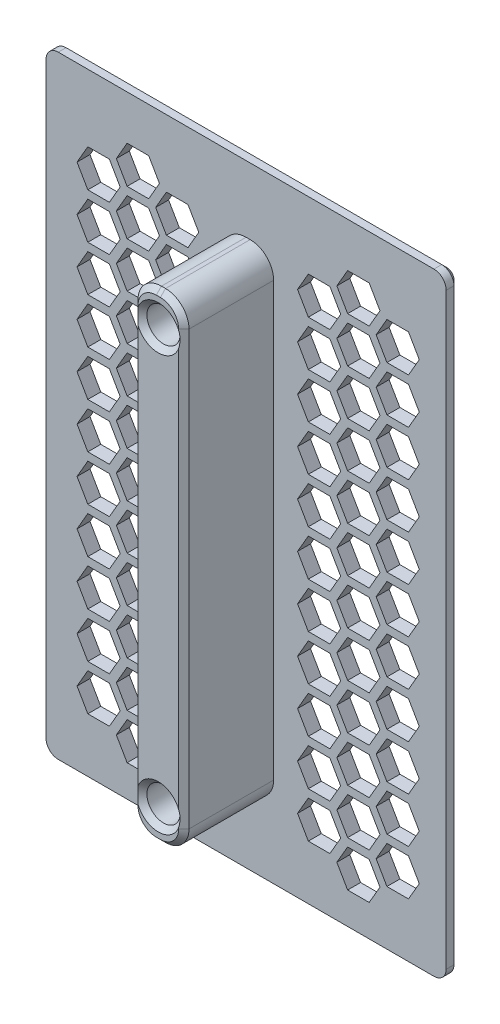
SolidWorks part; units mm, degrees
ref_plane "Front Plane" through (0, 0, 0) normal (0, 0, 1) x (1, 0, 0)
ref_plane "Top Plane" through (0, 0, 0) normal (0, 1, 0) x (1, 0, 0)
ref_plane "Right Plane" through (0, 0, 0) normal (1, 0, 0) x (0, 0, -1)
sketch "Sketch1" plane through (0, 0, 0) normal (0, 0, 1) x (1, 0, 0)
  line L0 (24.5, 37.5) -> (-24.5, 37.5) construction
  line L1 (24.5, -37.5) -> (-24.5, -37.5)
  line L2 (24.5, -37.5) -> (24.5, 37.5)
  line L3 (24.5, 37.5) -> (-24.5, 37.5)
  line L4 (-24.5, -37.5) -> (-24.5, 37.5)
  line L5 (24.5, -37.5) -> (-24.5, 37.5) construction
  line L6 (24.5, 37.5) -> (-24.5, -37.5) construction
  line L7 (24.5, 37.5) -> (24.5, -37.5) construction
  point P0 (0, 0)
extrude "Boss-Extrude1" add sketch "Sketch1" along normal blind 1.5875
sketch "Sketch2" plane through (0, 0, 1.5875) normal (0, 0, 1) x (1, 0, 0)
  line L12 (0.5, 29.5) -> (0, 29.5) construction
  line L13 (-3, 26.5) -> (-3, -26.5) construction
  line L14 (3.5, -26.5) -> (3.5, 26.5) construction
  line L15 (0, -29.5) -> (0.5, -29.5) construction
  line L16 (0.5, 29.5) -> (0, 29.5)
  line L17 (-3, 26.5) -> (-3, -26.5)
  line L18 (3.5, -26.5) -> (3.5, 26.5)
  line L19 (0, -29.5) -> (0.5, -29.5)
  line L20 (-2.873, 26.5) -> (-2.873, -26.5)
  line L21 (0, -29.373) -> (0.5, -29.373)
  line L22 (3.373, -26.5) -> (3.373, 26.5)
  line L23 (0.5, 29.373) -> (0, 29.373)
  arc A12 (3.5, 26.5) -> (0.5, 29.5) centre (0.5, 26.5) ccw construction
  arc A13 (0, 29.5) -> (-3, 26.5) centre (0, 26.5) ccw construction
  arc A14 (0.5, -29.5) -> (3.5, -26.5) centre (0.5, -26.5) ccw construction
  arc A15 (-3, -26.5) -> (0, -29.5) centre (0, -26.5) ccw construction
  arc A16 (3.5, 26.5) -> (0.5, 29.5) centre (0.5, 26.5) ccw
  arc A17 (0, 29.5) -> (-3, 26.5) centre (0, 26.5) ccw
  arc A18 (0.5, -29.5) -> (3.5, -26.5) centre (0.5, -26.5) ccw
  arc A19 (-3, -26.5) -> (0, -29.5) centre (0, -26.5) ccw
  arc A20 (0, 29.373) -> (-2.873, 26.5) centre (0, 26.5) ccw
  arc A21 (-2.873, -26.5) -> (0, -29.373) centre (0, -26.5) ccw
  arc A22 (0.5, -29.373) -> (3.373, -26.5) centre (0.5, -26.5) ccw
  arc A23 (3.373, 26.5) -> (0.5, 29.373) centre (0.5, 26.5) ccw
  dimension "D1" = 0.127
extrude "Boss-Extrude2" add sketch "Sketch2" along normal up to surface (11 mm away) contours L22 A23 L23 A20 L20 A21 L21 A22 region at (0.25, 0, 1.5875)
sketch "Sketch3" plane through (0, 0, 12.5875) normal (0, 0, 1) x (1, 0, 0)
  line L1 (0.25, 25.4) -> (0.25, -25.4) construction
  line L3 (-2.873, 0) -> (3.373, 0) construction
  line L4 (-2.873, -26.5) -> (-2.873, 26.5) construction
  line L5 (3.373, 26.5) -> (3.373, -26.5) construction
  circle A0 centre (0.25, 25.4) radius 2.032
  circle A1 centre (0.25, -25.4) radius 2.032
  point P13 (0.25, 0)
  point P14 (0, 0)
  dimension "D1" = 4.064
  dimension "D2" = 50.8
extrude "Cut-Extrude1" cut sketch "Sketch3" against normal blind 9.525
fillet "Fillet1" radius 1.5 4 edges at (24.5, -37.5, 0.7937) (-24.5, -37.5, 0.7937) (-24.5, 37.5, 0.7937) (24.5, 37.5, 0.7937)
sketch "Sketch4" plane through (0, 0, 0) normal (0, 0, -1) x (-1, 0, 0)
  line L0 (-18.5619, -28.5679) -> (-13.75, -31.346) construction
  line L1 (-16.3896, -31.346) -> (-15.0698, -33.632)
  line L2 (-15.0698, -33.632) -> (-12.4302, -33.632)
  line L3 (-12.4302, -33.632) -> (-11.1104, -31.346)
  line L4 (-11.1104, -31.346) -> (-12.4302, -29.06)
  line L5 (-12.4302, -29.06) -> (-15.0698, -29.06)
  line L6 (-15.0698, -29.06) -> (-16.3896, -31.346)
  line L7 (-21.2015, -28.5679) -> (-19.8817, -30.8539)
  line L8 (-19.8817, -30.8539) -> (-17.242, -30.8539)
  line L9 (-17.242, -30.8539) -> (-15.9222, -28.5679)
  line L10 (-15.9222, -28.5679) -> (-17.242, -26.2819)
  line L11 (-17.242, -26.2819) -> (-19.8817, -26.2819)
  line L12 (-19.8817, -26.2819) -> (-21.2015, -28.5679)
  line L13 (-10.258, -30.8539) -> (-7.6183, -30.8539)
  line L14 (-7.6183, -30.8539) -> (-6.2985, -28.5679)
  line L15 (-6.2985, -28.5679) -> (-7.6183, -26.2819)
  line L16 (-7.6183, -26.2819) -> (-10.258, -26.2819)
  line L17 (-10.258, -26.2819) -> (-11.5778, -28.5679)
  line L18 (-11.5778, -28.5679) -> (-10.258, -30.8539)
  line L19 (-11.1104, -31.346) -> (-10.258, -30.8539) construction
  line L20 (-13.75, -31.346) -> (-8.9381, -28.5679) construction
  line L21 (-4.5, -26.832) -> (-23, -26.832) construction
  line L22 (-10.258, -20.7257) -> (-11.5778, -23.0117)
  line L23 (-7.6183, -20.7257) -> (-10.258, -20.7257)
  line L24 (-6.2985, -23.0117) -> (-7.6183, -20.7257)
  line L25 (-7.6183, -25.2977) -> (-6.2985, -23.0117)
  line L26 (-10.258, -25.2977) -> (-7.6183, -25.2977)
  line L27 (-11.5778, -23.0117) -> (-10.258, -25.2977)
  line L28 (-11.1104, -25.7898) -> (-12.4302, -23.5038)
  line L29 (-12.4302, -23.5038) -> (-15.0698, -23.5038)
  line L30 (-15.0698, -23.5038) -> (-16.3896, -25.7898)
  line L31 (-16.3896, -25.7898) -> (-15.0698, -28.0758)
  line L32 (-15.0698, -28.0758) -> (-12.4302, -28.0758)
  line L33 (-12.4302, -28.0758) -> (-11.1104, -25.7898)
  line L34 (-17.242, -25.2977) -> (-15.9222, -23.0117)
  line L35 (-15.9222, -23.0117) -> (-17.242, -20.7257)
  line L36 (-17.242, -20.7257) -> (-19.8817, -20.7257)
  line L37 (-19.8817, -20.7257) -> (-21.2015, -23.0117)
  line L38 (-21.2015, -23.0117) -> (-19.8817, -25.2977)
  line L39 (-19.8817, -25.2977) -> (-17.242, -25.2977)
  line L40 (-10.258, -15.1694) -> (-11.5778, -17.4554)
  line L41 (-7.6183, -15.1694) -> (-10.258, -15.1694)
  line L42 (-6.2985, -17.4554) -> (-7.6183, -15.1694)
  line L43 (-7.6183, -19.7414) -> (-6.2985, -17.4554)
  line L44 (-10.258, -19.7414) -> (-7.6183, -19.7414)
  line L45 (-11.5778, -17.4554) -> (-10.258, -19.7414)
  line L46 (-11.1104, -20.2335) -> (-12.4302, -17.9475)
  line L47 (-12.4302, -17.9475) -> (-15.0698, -17.9475)
  line L48 (-15.0698, -17.9475) -> (-16.3896, -20.2335)
  line L49 (-16.3896, -20.2335) -> (-15.0698, -22.5195)
  line L50 (-15.0698, -22.5195) -> (-12.4302, -22.5195)
  line L51 (-12.4302, -22.5195) -> (-11.1104, -20.2335)
  line L52 (-17.242, -19.7414) -> (-15.9222, -17.4554)
  line L53 (-15.9222, -17.4554) -> (-17.242, -15.1694)
  line L54 (-17.242, -15.1694) -> (-19.8817, -15.1694)
  line L55 (-19.8817, -15.1694) -> (-21.2015, -17.4554)
  line L56 (-21.2015, -17.4554) -> (-19.8817, -19.7414)
  line L57 (-19.8817, -19.7414) -> (-17.242, -19.7414)
  line L58 (-10.258, -9.6132) -> (-11.5778, -11.8992)
  line L59 (-7.6183, -9.6132) -> (-10.258, -9.6132)
  line L60 (-6.2985, -11.8992) -> (-7.6183, -9.6132)
  line L61 (-7.6183, -14.1852) -> (-6.2985, -11.8992)
  line L62 (-10.258, -14.1852) -> (-7.6183, -14.1852)
  line L63 (-11.5778, -11.8992) -> (-10.258, -14.1852)
  line L64 (-11.1104, -14.6773) -> (-12.4302, -12.3913)
  line L65 (-12.4302, -12.3913) -> (-15.0698, -12.3913)
  line L66 (-15.0698, -12.3913) -> (-16.3896, -14.6773)
  line L67 (-16.3896, -14.6773) -> (-15.0698, -16.9633)
  line L68 (-15.0698, -16.9633) -> (-12.4302, -16.9633)
  line L69 (-12.4302, -16.9633) -> (-11.1104, -14.6773)
  line L70 (-17.242, -14.1852) -> (-15.9222, -11.8992)
  line L71 (-15.9222, -11.8992) -> (-17.242, -9.6132)
  line L72 (-17.242, -9.6132) -> (-19.8817, -9.6132)
  line L73 (-19.8817, -9.6132) -> (-21.2015, -11.8992)
  line L74 (-21.2015, -11.8992) -> (-19.8817, -14.1852)
  line L75 (-19.8817, -14.1852) -> (-17.242, -14.1852)
  line L76 (-10.258, -4.0569) -> (-11.5778, -6.3429)
  line L77 (-7.6183, -4.0569) -> (-10.258, -4.0569)
  line L78 (-6.2985, -6.3429) -> (-7.6183, -4.0569)
  line L79 (-7.6183, -8.6289) -> (-6.2985, -6.3429)
  line L80 (-10.258, -8.6289) -> (-7.6183, -8.6289)
  line L81 (-11.5778, -6.3429) -> (-10.258, -8.6289)
  line L82 (-11.1104, -9.121) -> (-12.4302, -6.835)
  line L83 (-12.4302, -6.835) -> (-15.0698, -6.835)
  line L84 (-15.0698, -6.835) -> (-16.3896, -9.121)
  line L85 (-16.3896, -9.121) -> (-15.0698, -11.407)
  line L86 (-15.0698, -11.407) -> (-12.4302, -11.407)
  line L87 (-12.4302, -11.407) -> (-11.1104, -9.121)
  line L88 (-17.242, -8.6289) -> (-15.9222, -6.3429)
  line L89 (-15.9222, -6.3429) -> (-17.242, -4.0569)
  line L90 (-17.242, -4.0569) -> (-19.8817, -4.0569)
  line L91 (-19.8817, -4.0569) -> (-21.2015, -6.3429)
  line L92 (-21.2015, -6.3429) -> (-19.8817, -8.6289)
  line L93 (-19.8817, -8.6289) -> (-17.242, -8.6289)
  line L94 (-10.258, 1.4993) -> (-11.5778, -0.7867)
  line L95 (-7.6183, 1.4993) -> (-10.258, 1.4993)
  line L96 (-6.2985, -0.7867) -> (-7.6183, 1.4993)
  line L97 (-7.6183, -3.0727) -> (-6.2985, -0.7867)
  line L98 (-10.258, -3.0727) -> (-7.6183, -3.0727)
  line L99 (-11.5778, -0.7867) -> (-10.258, -3.0727)
  line L100 (-11.1104, -3.5648) -> (-12.4302, -1.2788)
  line L101 (-12.4302, -1.2788) -> (-15.0698, -1.2788)
  line L102 (-15.0698, -1.2788) -> (-16.3896, -3.5648)
  line L103 (-16.3896, -3.5648) -> (-15.0698, -5.8508)
  line L104 (-15.0698, -5.8508) -> (-12.4302, -5.8508)
  line L105 (-12.4302, -5.8508) -> (-11.1104, -3.5648)
  line L106 (-17.242, -3.0727) -> (-15.9222, -0.7867)
  line L107 (-15.9222, -0.7867) -> (-17.242, 1.4993)
  line L108 (-17.242, 1.4993) -> (-19.8817, 1.4993)
  line L109 (-19.8817, 1.4993) -> (-21.2015, -0.7867)
  line L110 (-21.2015, -0.7867) -> (-19.8817, -3.0727)
  line L111 (-19.8817, -3.0727) -> (-17.242, -3.0727)
  line L112 (-10.258, 7.0556) -> (-11.5778, 4.7696)
  line L113 (-7.6183, 7.0556) -> (-10.258, 7.0556)
  line L114 (-6.2985, 4.7696) -> (-7.6183, 7.0556)
  line L115 (-7.6183, 2.4836) -> (-6.2985, 4.7696)
  line L116 (-10.258, 2.4836) -> (-7.6183, 2.4836)
  line L117 (-11.5778, 4.7696) -> (-10.258, 2.4836)
  line L118 (-11.1104, 1.9915) -> (-12.4302, 4.2775)
  line L119 (-12.4302, 4.2775) -> (-15.0698, 4.2775)
  line L120 (-15.0698, 4.2775) -> (-16.3896, 1.9915)
  line L121 (-16.3896, 1.9915) -> (-15.0698, -0.2945)
  line L122 (-15.0698, -0.2945) -> (-12.4302, -0.2945)
  line L123 (-12.4302, -0.2945) -> (-11.1104, 1.9915)
  line L124 (-17.242, 2.4836) -> (-15.9222, 4.7696)
  line L125 (-15.9222, 4.7696) -> (-17.242, 7.0556)
  line L126 (-17.242, 7.0556) -> (-19.8817, 7.0556)
  line L127 (-19.8817, 7.0556) -> (-21.2015, 4.7696)
  line L128 (-21.2015, 4.7696) -> (-19.8817, 2.4836)
  line L129 (-19.8817, 2.4836) -> (-17.242, 2.4836)
  line L130 (-10.258, 12.6118) -> (-11.5778, 10.3258)
  line L131 (-7.6183, 12.6118) -> (-10.258, 12.6118)
  line L132 (-6.2985, 10.3258) -> (-7.6183, 12.6118)
  line L133 (-7.6183, 8.0398) -> (-6.2985, 10.3258)
  line L134 (-10.258, 8.0398) -> (-7.6183, 8.0398)
  line L135 (-11.5778, 10.3258) -> (-10.258, 8.0398)
  line L136 (-11.1104, 7.5477) -> (-12.4302, 9.8337)
  line L137 (-12.4302, 9.8337) -> (-15.0698, 9.8337)
  line L138 (-15.0698, 9.8337) -> (-16.3896, 7.5477)
  line L139 (-16.3896, 7.5477) -> (-15.0698, 5.2617)
  line L140 (-15.0698, 5.2617) -> (-12.4302, 5.2617)
  line L141 (-12.4302, 5.2617) -> (-11.1104, 7.5477)
  line L142 (-17.242, 8.0398) -> (-15.9222, 10.3258)
  line L143 (-15.9222, 10.3258) -> (-17.242, 12.6118)
  line L144 (-17.242, 12.6118) -> (-19.8817, 12.6118)
  line L145 (-19.8817, 12.6118) -> (-21.2015, 10.3258)
  line L146 (-21.2015, 10.3258) -> (-19.8817, 8.0398)
  line L147 (-19.8817, 8.0398) -> (-17.242, 8.0398)
  line L148 (-10.258, 18.1681) -> (-11.5778, 15.8821)
  line L149 (-7.6183, 18.1681) -> (-10.258, 18.1681)
  line L150 (-6.2985, 15.8821) -> (-7.6183, 18.1681)
  line L151 (-7.6183, 13.5961) -> (-6.2985, 15.8821)
  line L152 (-10.258, 13.5961) -> (-7.6183, 13.5961)
  line L153 (-11.5778, 15.8821) -> (-10.258, 13.5961)
  line L154 (-11.1104, 13.104) -> (-12.4302, 15.39)
  line L155 (-12.4302, 15.39) -> (-15.0698, 15.39)
  line L156 (-15.0698, 15.39) -> (-16.3896, 13.104)
  line L157 (-16.3896, 13.104) -> (-15.0698, 10.818)
  line L158 (-15.0698, 10.818) -> (-12.4302, 10.818)
  line L159 (-12.4302, 10.818) -> (-11.1104, 13.104)
  line L160 (-17.242, 13.5961) -> (-15.9222, 15.8821)
  line L161 (-15.9222, 15.8821) -> (-17.242, 18.1681)
  line L162 (-17.242, 18.1681) -> (-19.8817, 18.1681)
  line L163 (-19.8817, 18.1681) -> (-21.2015, 15.8821)
  line L164 (-21.2015, 15.8821) -> (-19.8817, 13.5961)
  line L165 (-19.8817, 13.5961) -> (-17.242, 13.5961)
  line L166 (-10.258, 23.7243) -> (-11.5778, 21.4383)
  line L167 (-7.6183, 23.7243) -> (-10.258, 23.7243)
  line L168 (-6.2985, 21.4383) -> (-7.6183, 23.7243)
  line L169 (-7.6183, 19.1523) -> (-6.2985, 21.4383)
  line L170 (-10.258, 19.1523) -> (-7.6183, 19.1523)
  line L171 (-11.5778, 21.4383) -> (-10.258, 19.1523)
  line L172 (-11.1104, 18.6602) -> (-12.4302, 20.9462)
  line L173 (-12.4302, 20.9462) -> (-15.0698, 20.9462)
  line L174 (-15.0698, 20.9462) -> (-16.3896, 18.6602)
  line L175 (-16.3896, 18.6602) -> (-15.0698, 16.3742)
  line L176 (-15.0698, 16.3742) -> (-12.4302, 16.3742)
  line L177 (-12.4302, 16.3742) -> (-11.1104, 18.6602)
  line L178 (-17.242, 19.1523) -> (-15.9222, 21.4383)
  line L179 (-15.9222, 21.4383) -> (-17.242, 23.7243)
  line L180 (-17.242, 23.7243) -> (-19.8817, 23.7243)
  line L181 (-19.8817, 23.7243) -> (-21.2015, 21.4383)
  line L182 (-21.2015, 21.4383) -> (-19.8817, 19.1523)
  line L183 (-19.8817, 19.1523) -> (-17.242, 19.1523)
  line L202 (-11.5778, -28.5679) -> (-12.4302, -28.0758) construction
  line L203 (-0.25, 25.4) -> (-0.25, -25.4) construction
  line L206 (16.0821, 28.1376) -> (15.2297, 28.6297) construction
  line L207 (13.25, 27.4867) -> (13.25, 26.5025) construction
  line L208 (11.0778, -28.5679) -> (11.9302, -28.0758) construction
  line L209 (4, -26.832) -> (22.5, -26.832) construction
  line L410 (13.25, -31.346) -> (8.4381, -28.5679) construction
  line L419 (-10.258, 29.2806) -> (-11.5778, 26.9946)
  line L426 (-7.6183, 29.2806) -> (-10.258, 29.2806)
  line L427 (-6.2985, 26.9946) -> (-7.6183, 29.2806)
  line L434 (-7.6183, 24.7086) -> (-6.2985, 26.9946)
  line L441 (-4.5, -21.3426) -> (-4.5, -12.1527) construction
  line L442 (-23, -37.5) -> (-19.952, -37.5) construction
  line L443 (-23, -12.7255) -> (-23, -21.3426) construction
  line L444 (-10.258, 24.7086) -> (-7.6183, 24.7086)
  line L445 (-11.5778, 26.9946) -> (-10.258, 24.7086)
  line L446 (-11.1104, 24.2165) -> (-12.4302, 26.5025)
  line L447 (-12.4302, 26.5025) -> (-15.0698, 26.5025)
  line L448 (-15.0698, 26.5025) -> (-16.3896, 24.2165)
  line L449 (-16.3896, 24.2165) -> (-15.0698, 21.9305)
  line L450 (-15.0698, 21.9305) -> (-12.4302, 21.9305)
  line L451 (-12.4302, 21.9305) -> (-11.1104, 24.2165)
  line L452 (-17.242, 24.7086) -> (-15.9222, 26.9946)
  line L453 (-15.9222, 26.9946) -> (-17.242, 29.2806)
  line L454 (-17.242, 29.2806) -> (-19.8817, 29.2806)
  line L455 (-19.8817, 29.2806) -> (-21.2015, 26.9946)
  line L456 (-21.2015, 26.9946) -> (-19.8817, 24.7086)
  line L457 (-19.8817, 24.7086) -> (-17.242, 24.7086)
  line L477 (10.6104, -31.346) -> (9.758, -30.8539) construction
  line L489 (-13.75, 27.4867) -> (-13.75, 26.5025) construction
  line L491 (-16.5821, 28.1376) -> (-15.7297, 28.6297) construction
  line L492 (-11.1104, 29.7727) -> (-12.4302, 32.0587)
  line L493 (-12.4302, 32.0587) -> (-15.0698, 32.0587)
  line L494 (-15.0698, 32.0587) -> (-16.3896, 29.7727)
  line L495 (-16.3896, 29.7727) -> (-15.0698, 27.4867)
  line L496 (-15.0698, 27.4867) -> (-12.4302, 27.4867)
  line L497 (-12.4302, 27.4867) -> (-11.1104, 29.7727)
  line L498 (18.0619, -28.5679) -> (13.25, -31.346) construction
  line L505 (11.9302, 27.4867) -> (10.6104, 29.7727)
  line L533 (-0.25, 25.4) -> (-0.25, -25.4)
  line L534 (14.5698, 27.4867) -> (11.9302, 27.4867)
  line L535 (15.8896, 29.7727) -> (14.5698, 27.4867)
  line L536 (14.5698, 32.0587) -> (15.8896, 29.7727)
  line L537 (11.9302, 32.0587) -> (14.5698, 32.0587)
  line L538 (10.6104, 29.7727) -> (11.9302, 32.0587)
  line L539 (19.3817, 24.7086) -> (16.742, 24.7086)
  line L540 (20.7015, 26.9946) -> (19.3817, 24.7086)
  line L541 (19.3817, 29.2806) -> (20.7015, 26.9946)
  line L542 (16.742, 29.2806) -> (19.3817, 29.2806)
  line L543 (15.4222, 26.9946) -> (16.742, 29.2806)
  line L544 (16.742, 24.7086) -> (15.4222, 26.9946)
  line L545 (11.9302, 21.9305) -> (10.6104, 24.2165)
  line L546 (14.5698, 21.9305) -> (11.9302, 21.9305)
  line L547 (15.8896, 24.2165) -> (14.5698, 21.9305)
  line L548 (14.5698, 26.5025) -> (15.8896, 24.2165)
  line L549 (11.9302, 26.5025) -> (14.5698, 26.5025)
  line L550 (10.6104, 24.2165) -> (11.9302, 26.5025)
  line L551 (11.0778, 26.9946) -> (9.758, 24.7086)
  line L552 (9.758, 24.7086) -> (7.1183, 24.7086)
  line L553 (7.1183, 24.7086) -> (5.7985, 26.9946)
  line L554 (5.7985, 26.9946) -> (7.1183, 29.2806)
  line L555 (7.1183, 29.2806) -> (9.758, 29.2806)
  line L556 (9.758, 29.2806) -> (11.0778, 26.9946)
  line L557 (19.3817, 19.1523) -> (16.742, 19.1523)
  line L558 (20.7015, 21.4383) -> (19.3817, 19.1523)
  line L559 (19.3817, 23.7243) -> (20.7015, 21.4383)
  line L560 (16.742, 23.7243) -> (19.3817, 23.7243)
  line L561 (15.4222, 21.4383) -> (16.742, 23.7243)
  line L562 (16.742, 19.1523) -> (15.4222, 21.4383)
  line L563 (11.9302, 16.3742) -> (10.6104, 18.6602)
  line L564 (14.5698, 16.3742) -> (11.9302, 16.3742)
  line L565 (15.8896, 18.6602) -> (14.5698, 16.3742)
  line L566 (14.5698, 20.9462) -> (15.8896, 18.6602)
  line L567 (11.9302, 20.9462) -> (14.5698, 20.9462)
  line L568 (10.6104, 18.6602) -> (11.9302, 20.9462)
  line L569 (11.0778, 21.4383) -> (9.758, 19.1523)
  line L570 (9.758, 19.1523) -> (7.1183, 19.1523)
  line L571 (7.1183, 19.1523) -> (5.7985, 21.4383)
  line L572 (5.7985, 21.4383) -> (7.1183, 23.7243)
  line L573 (7.1183, 23.7243) -> (9.758, 23.7243)
  line L574 (9.758, 23.7243) -> (11.0778, 21.4383)
  line L575 (19.3817, 13.5961) -> (16.742, 13.5961)
  line L576 (20.7015, 15.8821) -> (19.3817, 13.5961)
  line L577 (19.3817, 18.1681) -> (20.7015, 15.8821)
  line L578 (16.742, 18.1681) -> (19.3817, 18.1681)
  line L579 (15.4222, 15.8821) -> (16.742, 18.1681)
  line L580 (16.742, 13.5961) -> (15.4222, 15.8821)
  line L581 (11.9302, 10.818) -> (10.6104, 13.104)
  line L582 (14.5698, 10.818) -> (11.9302, 10.818)
  line L583 (15.8896, 13.104) -> (14.5698, 10.818)
  line L584 (14.5698, 15.39) -> (15.8896, 13.104)
  line L585 (11.9302, 15.39) -> (14.5698, 15.39)
  line L586 (10.6104, 13.104) -> (11.9302, 15.39)
  line L587 (11.0778, 15.8821) -> (9.758, 13.5961)
  line L588 (9.758, 13.5961) -> (7.1183, 13.5961)
  line L589 (7.1183, 13.5961) -> (5.7985, 15.8821)
  line L590 (5.7985, 15.8821) -> (7.1183, 18.1681)
  line L591 (7.1183, 18.1681) -> (9.758, 18.1681)
  line L592 (9.758, 18.1681) -> (11.0778, 15.8821)
  line L593 (19.3817, 8.0398) -> (16.742, 8.0398)
  line L594 (20.7015, 10.3258) -> (19.3817, 8.0398)
  line L595 (19.3817, 12.6118) -> (20.7015, 10.3258)
  line L596 (16.742, 12.6118) -> (19.3817, 12.6118)
  line L597 (15.4222, 10.3258) -> (16.742, 12.6118)
  line L598 (16.742, 8.0398) -> (15.4222, 10.3258)
  line L599 (11.9302, 5.2617) -> (10.6104, 7.5477)
  line L600 (14.5698, 5.2617) -> (11.9302, 5.2617)
  line L601 (15.8896, 7.5477) -> (14.5698, 5.2617)
  line L602 (14.5698, 9.8337) -> (15.8896, 7.5477)
  line L603 (11.9302, 9.8337) -> (14.5698, 9.8337)
  line L604 (10.6104, 7.5477) -> (11.9302, 9.8337)
  line L605 (11.0778, 10.3258) -> (9.758, 8.0398)
  line L606 (9.758, 8.0398) -> (7.1183, 8.0398)
  line L607 (7.1183, 8.0398) -> (5.7985, 10.3258)
  line L608 (5.7985, 10.3258) -> (7.1183, 12.6118)
  line L609 (7.1183, 12.6118) -> (9.758, 12.6118)
  line L610 (9.758, 12.6118) -> (11.0778, 10.3258)
  line L611 (19.3817, 2.4836) -> (16.742, 2.4836)
  line L612 (20.7015, 4.7696) -> (19.3817, 2.4836)
  line L613 (19.3817, 7.0556) -> (20.7015, 4.7696)
  line L614 (16.742, 7.0556) -> (19.3817, 7.0556)
  line L615 (15.4222, 4.7696) -> (16.742, 7.0556)
  line L616 (16.742, 2.4836) -> (15.4222, 4.7696)
  line L617 (11.9302, -0.2945) -> (10.6104, 1.9915)
  line L618 (14.5698, -0.2945) -> (11.9302, -0.2945)
  line L619 (15.8896, 1.9915) -> (14.5698, -0.2945)
  line L620 (14.5698, 4.2775) -> (15.8896, 1.9915)
  line L621 (11.9302, 4.2775) -> (14.5698, 4.2775)
  line L622 (10.6104, 1.9915) -> (11.9302, 4.2775)
  line L623 (11.0778, 4.7696) -> (9.758, 2.4836)
  line L624 (9.758, 2.4836) -> (7.1183, 2.4836)
  line L625 (7.1183, 2.4836) -> (5.7985, 4.7696)
  line L626 (5.7985, 4.7696) -> (7.1183, 7.0556)
  line L627 (7.1183, 7.0556) -> (9.758, 7.0556)
  line L628 (9.758, 7.0556) -> (11.0778, 4.7696)
  line L629 (19.3817, -3.0727) -> (16.742, -3.0727)
  line L630 (20.7015, -0.7867) -> (19.3817, -3.0727)
  line L631 (19.3817, 1.4993) -> (20.7015, -0.7867)
  line L632 (16.742, 1.4993) -> (19.3817, 1.4993)
  line L633 (15.4222, -0.7867) -> (16.742, 1.4993)
  line L634 (16.742, -3.0727) -> (15.4222, -0.7867)
  line L635 (11.9302, -5.8508) -> (10.6104, -3.5648)
  line L636 (14.5698, -5.8508) -> (11.9302, -5.8508)
  line L637 (15.8896, -3.5648) -> (14.5698, -5.8508)
  line L638 (14.5698, -1.2788) -> (15.8896, -3.5648)
  line L639 (11.9302, -1.2788) -> (14.5698, -1.2788)
  line L640 (10.6104, -3.5648) -> (11.9302, -1.2788)
  line L641 (11.0778, -0.7867) -> (9.758, -3.0727)
  line L642 (9.758, -3.0727) -> (7.1183, -3.0727)
  line L643 (7.1183, -3.0727) -> (5.7985, -0.7867)
  line L644 (5.7985, -0.7867) -> (7.1183, 1.4993)
  line L645 (7.1183, 1.4993) -> (9.758, 1.4993)
  line L646 (9.758, 1.4993) -> (11.0778, -0.7867)
  line L647 (19.3817, -8.6289) -> (16.742, -8.6289)
  line L648 (20.7015, -6.3429) -> (19.3817, -8.6289)
  line L649 (19.3817, -4.0569) -> (20.7015, -6.3429)
  line L650 (16.742, -4.0569) -> (19.3817, -4.0569)
  line L651 (15.4222, -6.3429) -> (16.742, -4.0569)
  line L652 (16.742, -8.6289) -> (15.4222, -6.3429)
  line L653 (11.9302, -11.407) -> (10.6104, -9.121)
  line L654 (14.5698, -11.407) -> (11.9302, -11.407)
  line L655 (15.8896, -9.121) -> (14.5698, -11.407)
  line L656 (14.5698, -6.835) -> (15.8896, -9.121)
  line L657 (11.9302, -6.835) -> (14.5698, -6.835)
  line L658 (10.6104, -9.121) -> (11.9302, -6.835)
  line L659 (11.0778, -6.3429) -> (9.758, -8.6289)
  line L660 (9.758, -8.6289) -> (7.1183, -8.6289)
  line L661 (7.1183, -8.6289) -> (5.7985, -6.3429)
  line L662 (5.7985, -6.3429) -> (7.1183, -4.0569)
  line L663 (7.1183, -4.0569) -> (9.758, -4.0569)
  line L664 (9.758, -4.0569) -> (11.0778, -6.3429)
  line L665 (19.3817, -14.1852) -> (16.742, -14.1852)
  line L666 (20.7015, -11.8992) -> (19.3817, -14.1852)
  line L667 (19.3817, -9.6132) -> (20.7015, -11.8992)
  line L668 (16.742, -9.6132) -> (19.3817, -9.6132)
  line L669 (15.4222, -11.8992) -> (16.742, -9.6132)
  line L670 (16.742, -14.1852) -> (15.4222, -11.8992)
  line L671 (11.9302, -16.9633) -> (10.6104, -14.6773)
  line L672 (14.5698, -16.9633) -> (11.9302, -16.9633)
  line L673 (15.8896, -14.6773) -> (14.5698, -16.9633)
  line L674 (14.5698, -12.3913) -> (15.8896, -14.6773)
  line L675 (11.9302, -12.3913) -> (14.5698, -12.3913)
  line L676 (10.6104, -14.6773) -> (11.9302, -12.3913)
  line L677 (11.0778, -11.8992) -> (9.758, -14.1852)
  line L678 (9.758, -14.1852) -> (7.1183, -14.1852)
  line L679 (7.1183, -14.1852) -> (5.7985, -11.8992)
  line L680 (5.7985, -11.8992) -> (7.1183, -9.6132)
  line L681 (7.1183, -9.6132) -> (9.758, -9.6132)
  line L682 (9.758, -9.6132) -> (11.0778, -11.8992)
  line L683 (19.3817, -19.7414) -> (16.742, -19.7414)
  line L684 (20.7015, -17.4554) -> (19.3817, -19.7414)
  line L685 (19.3817, -15.1694) -> (20.7015, -17.4554)
  line L686 (16.742, -15.1694) -> (19.3817, -15.1694)
  line L687 (15.4222, -17.4554) -> (16.742, -15.1694)
  line L688 (16.742, -19.7414) -> (15.4222, -17.4554)
  line L689 (11.9302, -22.5195) -> (10.6104, -20.2335)
  line L690 (14.5698, -22.5195) -> (11.9302, -22.5195)
  line L691 (15.8896, -20.2335) -> (14.5698, -22.5195)
  line L692 (14.5698, -17.9475) -> (15.8896, -20.2335)
  line L693 (11.9302, -17.9475) -> (14.5698, -17.9475)
  line L694 (10.6104, -20.2335) -> (11.9302, -17.9475)
  line L695 (11.0778, -17.4554) -> (9.758, -19.7414)
  line L696 (9.758, -19.7414) -> (7.1183, -19.7414)
  line L697 (7.1183, -19.7414) -> (5.7985, -17.4554)
  line L698 (5.7985, -17.4554) -> (7.1183, -15.1694)
  line L699 (7.1183, -15.1694) -> (9.758, -15.1694)
  line L700 (9.758, -15.1694) -> (11.0778, -17.4554)
  line L701 (19.3817, -25.2977) -> (16.742, -25.2977)
  line L702 (20.7015, -23.0117) -> (19.3817, -25.2977)
  line L703 (19.3817, -20.7257) -> (20.7015, -23.0117)
  line L704 (16.742, -20.7257) -> (19.3817, -20.7257)
  line L705 (15.4222, -23.0117) -> (16.742, -20.7257)
  line L706 (16.742, -25.2977) -> (15.4222, -23.0117)
  line L707 (11.9302, -28.0758) -> (10.6104, -25.7898)
  line L708 (14.5698, -28.0758) -> (11.9302, -28.0758)
  line L709 (15.8896, -25.7898) -> (14.5698, -28.0758)
  line L710 (14.5698, -23.5038) -> (15.8896, -25.7898)
  line L711 (11.9302, -23.5038) -> (14.5698, -23.5038)
  line L712 (10.6104, -25.7898) -> (11.9302, -23.5038)
  line L713 (11.0778, -23.0117) -> (9.758, -25.2977)
  line L714 (9.758, -25.2977) -> (7.1183, -25.2977)
  line L715 (7.1183, -25.2977) -> (5.7985, -23.0117)
  line L716 (5.7985, -23.0117) -> (7.1183, -20.7257)
  line L717 (7.1183, -20.7257) -> (9.758, -20.7257)
  line L718 (9.758, -20.7257) -> (11.0778, -23.0117)
  line L719 (11.0778, -28.5679) -> (9.758, -30.8539)
  line L720 (9.758, -26.2819) -> (11.0778, -28.5679)
  line L721 (7.1183, -26.2819) -> (9.758, -26.2819)
  line L722 (5.7985, -28.5679) -> (7.1183, -26.2819)
  line L723 (7.1183, -30.8539) -> (5.7985, -28.5679)
  line L724 (9.758, -30.8539) -> (7.1183, -30.8539)
  line L725 (19.3817, -26.2819) -> (20.7015, -28.5679)
  line L726 (16.742, -26.2819) -> (19.3817, -26.2819)
  line L727 (15.4222, -28.5679) -> (16.742, -26.2819)
  line L728 (16.742, -30.8539) -> (15.4222, -28.5679)
  line L729 (19.3817, -30.8539) -> (16.742, -30.8539)
  line L730 (20.7015, -28.5679) -> (19.3817, -30.8539)
  line L731 (14.5698, -29.06) -> (15.8896, -31.346)
  line L732 (11.9302, -29.06) -> (14.5698, -29.06)
  line L733 (10.6104, -31.346) -> (11.9302, -29.06)
  line L734 (11.9302, -33.632) -> (10.6104, -31.346)
  line L735 (14.5698, -33.632) -> (11.9302, -33.632)
  line L736 (15.8896, -31.346) -> (14.5698, -33.632)
  circle A0 centre (-13.75, -31.346) radius 2.286 construction
  circle A1 centre (-18.5619, -28.5679) radius 2.286 construction
  circle A2 centre (-8.9381, -28.5679) radius 2.286 construction
  circle A11 centre (-13.75, 29.7727) radius 2.286 construction
  circle A12 centre (13.25, 29.7727) radius 2.286 construction
  circle A13 centre (8.4381, -28.5679) radius 2.286 construction
  circle A14 centre (18.0619, -28.5679) radius 2.286 construction
  circle A15 centre (13.25, -31.346) radius 2.286 construction
  point P28 (-13.75, -26.832)
  dimension "D1" = 4.572
  dimension "D2" = 5.5562
  dimension "D3" = 4.514
  dimension "D8" = 10.668
  dimension "D4" = 11
extrude "Cut-Extrude2" cut sketch "Sketch4" against normal up to next (1.5875 mm away) contours L51 L46 L47 L48 L49 L50 | L39 L34 L35 L36 L37 L38 | L12 L7 L8 L9 L10 L11 | L30 L31 L32 L33 L28 L29 | L6 L1 L2 L3 L4 L5 | L17 L18 L13 L14 L15 L16 | L27 L26 L25 L24 L23 L22 | L44 L43 L42 L41 L40 L45 | L68 L69 L64 L65 L66 L67 | L52 L53 L54 L55 L56 L57 | L62 L61 L60 L59 L58 L63 | L75 L70 L71 L72 L73 L74 | L86 L87 L82 L83 L84 L85 | L80 L79 L78 L77 L76 L81 | L104 L105 L100 L101 L102 L103 | L93 L88 L89 L90 L91 L92 | L111 L106 L107 L108 L109 L110 | L129 L124 L125 L126 L127 L128 | L122 L123 L118 L119 L120 L121 | L98 L97 L96 L95 L94 L99 | L116 L115 L114 L113 L112 L117 | L140 L141 L136 L137 L138 L139 | L147 L142 L143 L144 L145 L146 | L165 L160 L161 L162 L163 L164 | L183 L178 L179 L180 L181 L182 | L457 L452 L453 L454 L455 L456 | L496 L497 L492 L493 L494 L495 | L447 L448 L449 L450 L451 L446 | L426 L419 L445 L444 L434 L427 | L167 L166 L171 L170 L169 L168 | L173 L174 L175 L176 L177 L172 | L155 L156 L157 L158 L159 L154 | L149 L148 L153 L152 L151 L150 | L131 L130 L135 L134 L133 L132 | L555 L556 L551 L552 L553 L554 | L539 L544 L543 L542 L541 L540 | L535 L534 L505 L538 L537 L536 | L548 L547 L546 L545 L550 L549 | L561 L560 L559 L558 L557 L562 | L570 L571 L572 L573 L574 L569 | L588 L589 L590 L591 L592 L587 | L564 L563 L568 L567 L566 L565 | L575 L580 L579 L578 L577 L576 | L582 L581 L586 L585 L584 L583 | L606 L607 L608 L609 L610 L605 | L600 L599 L604 L603 L602 L601 | L593 L598 L597 L596 L595 L594 | L624 L625 L626 L627 L628 L623 | L611 L616 L615 L614 L613 L612 | L618 L617 L622 L621 L620 L619 | L642 L643 L644 L645 L646 L641 | L636 L635 L640 L639 L638 L637 | L629 L634 L633 L632 L631 L630 | L660 L661 L662 L663 L664 L659 | L654 L653 L658 L657 L656 L655 | L647 L652 L651 L650 L649 L648 | L665 L670 L669 L668 L667 L666 | L678 L679 L680 L681 L682 L677 | L672 L671 L676 L675 L674 L673 | L696 L697 L698 L699 L700 L695 | L690 L689 L694 L693 L692 L691 | L683 L688 L687 L686 L685 L684 | L704 L703 L702 L701 L706 L705 | L717 L718 L713 L714 L715 L716 | L711 L710 L709 L708 L707 L712 | L722 L721 L720 L719 L724 L723 | L735 L734 L733 L732 L731 L736 | L729 L728 L727 L726 L725 L730
chamfer "Chamfer1" distance 0.635 angle 45 18 edges at (-24.5, 0, 0) (-24.0607, -37.0607, 0) (-24.0607, 37.0607, 0) (0, -37.5, 0) (0, 37.5, 0) (24.0607, -37.0607, 0) (24.0607, 37.0607, 0) (24.5, 0, 0) (2.282, -25.4, 12.5875) (2.282, 25.4, 12.5875) (-2.873, 0, 12.5875) (-2.0315, 28.5315, 12.5875) (-2.0315, -28.5315, 12.5875) (0.25, 29.373, 12.5875) (0.25, -29.373, 12.5875) (2.5315, 28.5315, 12.5875) (2.5315, -28.5315, 12.5875) (3.373, 0, 12.5875)
